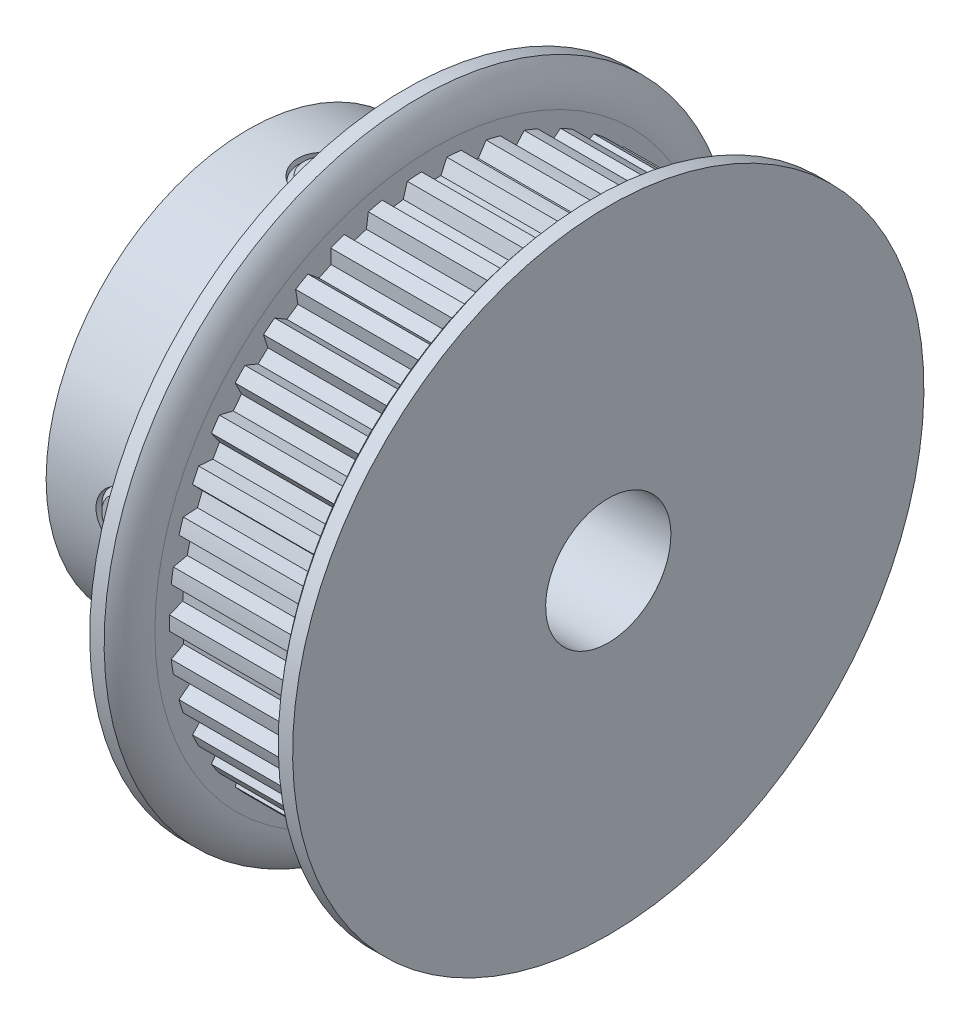
SolidWorks part; units mm, degrees
ref_plane "Front Plane" through (0, 0, 0) normal (0, 0, 1) x (1, 0, 0)
ref_plane "Top Plane" through (0, 0, 0) normal (0, 1, 0) x (1, 0, 0)
ref_plane "Right Plane" through (0, 0, 0) normal (1, 0, 0) x (0, 0, -1)
sketch "Sketch2" plane through (0, 0, 0) normal (1, 0, 0) x (0, 0, -1)
  line L3 (0, 0) -> (0, 12.7635) construction
  line L6 (0, -13.2715) -> (0, -13.589) construction
  line L7 (-0.5715, 13.2592) -> (-0.3383, 12.759)
  line L8 (0.5715, 13.2592) -> (0.3383, 12.759)
  line L9 (-0.5715, 13.2592) -> (-0.6441, 13.4148)
  line L10 (0.5715, 13.2592) -> (0.6441, 13.4148)
  line L12 (-0.3383, 12.759) -> (0.3383, 12.759)
  line L14 (0, 13.2715) -> (0, 13.589) construction
  line L15 (0, 0) -> (0, -1.143) construction
  circle A0 centre (0, 0) radius 13.589 construction
  circle A1 centre (0, 0) radius 12.7635 construction
  circle A2 centre (0, 0) radius 13.2715 construction
  arc A7 (0.6441, 13.4148) -> (-0.6441, 13.4148) centre (0, 0) ccw
  point P5 (0, 13.4303)
  dimension "D1" = 50
  dimension "PD" = 27.178
  dimension "D3" = 0.3175
  dimension "bt" = 1.143
  dimension "hs" = 1.143
  dimension "ht" = 0.508
sketch "Sketch1" plane through (0, 0, 0) normal (0, 0, 1) x (1, 0, 0)
  line L0 (-9.1313, 0) -> (9.1313, 0) construction
  line L1 (-9.1313, 3.175) -> (9.1313, 3.175)
  line L2 (-9.1313, 3.175) -> (-9.1313, 10.2362)
  line L3 (-1.1557, 16.002) -> (-0.4254, 16.002)
  line L4 (0.3048, 13.589) -> (0.3048, 14.1605)
  line L5 (0.3048, 14.732) -> (0.3048, 13.589) construction
  line L6 (0.3048, 13.589) -> (7.6708, 13.589)
  line L7 (7.6708, 13.589) -> (7.6708, 14.1605)
  line L8 (7.6708, 13.589) -> (9.1313, 13.589) construction
  line L9 (8.4011, 16.002) -> (9.1313, 16.002)
  line L10 (9.1313, 16.002) -> (9.1313, 3.175)
  line L11 (8.4011, 13.589) -> (8.4011, 16.002) construction
  line L12 (-5.1435, 10.2362) -> (-5.1435, 3.175) construction
  line L13 (-1.1557, 16.002) -> (-1.1557, 10.2362)
  line L14 (-1.1557, 10.2362) -> (-9.1313, 10.2362)
  arc A0 (7.6708, 14.1605) -> (8.4011, 16.002) centre (10.3578, 14.1605) cw
  arc A1 (0.3048, 14.1605) -> (-0.4254, 16.002) centre (-2.3822, 14.1605) ccw
  dimension "Bore Size" = 6.35
  dimension "D2" = 27.178
  dimension "Overall Width" = 18.2626
  dimension "Inside Width" = 7.366
  dimension "Outside Width" = 10.287
  dimension "Hub Dia" = 20.4724
  dimension "OD" = 32.004
  dimension "D3" = 1.143
  dimension "D4" = 0.5715
revolve "Revolve1" add sketch "Sketch1" angle 360 mid plane about L0
sketch "Sketch4" plane through (0.3048, 0, 0) normal (1, 0, 0) x (0, 0, -1)
  circle A0 centre (0, 0) radius 13.4303
  circle A2 centre (0, 0) radius 13.589
  circle A3 centre (0, 0) radius 13.589 construction
extrude "Cut-Extrude2" cut sketch "Sketch4" along normal up to surface (7.366 mm away) up to face at (7.6708, -13.589, 0)
sketch "Sketch3" plane through (0.3048, 0, 0) normal (1, 0, 0) x (0, 0, -1)
  line L2 (-0.5715, 13.2592) -> (-0.3383, 12.759) construction
  line L3 (-0.3383, 12.759) -> (0.3383, 12.759) construction
  line L4 (0.5715, 13.2592) -> (0.3383, 12.759) construction
  line L5 (-0.6441, 13.4148) -> (-0.3383, 12.759)
  line L6 (-0.3383, 12.759) -> (0.3383, 12.759)
  line L7 (0.6441, 13.4148) -> (0.3383, 12.759)
  arc A1 (0.6441, 13.4148) -> (-0.6441, 13.4148) centre (0, 0) ccw construction
  arc A2 (0.6441, 13.4148) -> (-0.6441, 13.4148) centre (0, 0) ccw
extrude "Cut-Extrude1" cut sketch "Sketch3" along normal up to surface (7.366 mm away) up to face at (7.6708, -14.1605, 0)
pattern_circular "CirPattern1" count 42 over 360 of "Cut-Extrude1"
sketch "Sketch5" plane through (0, 0, 0) normal (0, 0, 1) x (1, 0, 0)
  line L1 (7.6708, 14.1605) -> (7.6708, -14.1605) construction
  point P0 (7.6708, 0)
sketch "Sketch6" plane through (0, 0, 0) normal (0, 1, 0) x (1, 0, 0)
  line L0 (-9.1313, 0) -> (-6.604, 0) construction
  line L1 (-9.1313, 16.002) -> (-9.1313, -16.002) construction
  line L2 (-1.1557, 0) -> (-3.683, 0) construction
  line L4 (-1.1557, 16.002) -> (-1.1557, -16.002) construction
  circle A0 centre (-5.1435, 0) radius 1.4605
  dimension "D1" = 2.921
extrude "Cut-Extrude3" cut sketch "Sketch6" along normal through all
sketch "Sketch7" plane through (0, 0, 0) normal (0, 0, 1) x (1, 0, 0)
  line L0 (-6.3119, 10.2362) -> (-5.1435, 10.2362)
  line L1 (-6.5659, 9.9822) -> (-6.5659, 3.81)
  line L2 (-6.5659, 3.81) -> (-6.3119, 3.556)
  line L3 (-6.3119, 3.556) -> (-5.1435, 3.556)
  line L4 (-5.1435, 3.556) -> (-5.1435, 10.2362) construction
  line L5 (-1.1557, 10.2362) -> (-9.1313, 10.2362) construction
  line L6 (-6.5659, 9.9822) -> (-6.3119, 10.2362)
  line L8 (-5.1435, 10.2362) -> (-5.1435, 3.556)
  point P0 (-6.5659, 10.2362)
  point P4 (-6.5659, 3.556)
  dimension "D1" = 2.8448
  dimension "D2" = 0.381
revolve "Revolve2" add sketch "Sketch7" angle 360 mid plane about L4
sketch "Sketch8" plane through (0, 10.2362, 0) normal (0, 1, 0) x (1, 0, 0)
  line L1 (-5.1435, 0.8212) -> (-5.8547, 0.4106)
  line L2 (-5.8547, 0.4106) -> (-5.8547, -0.4106)
  line L3 (-5.8547, -0.4106) -> (-5.1435, -0.8212)
  line L4 (-5.1435, -0.8212) -> (-4.4323, -0.4106)
  line L5 (-4.4323, -0.4106) -> (-4.4323, 0.4106)
  line L6 (-4.4323, 0.4106) -> (-5.1435, 0.8212)
  circle A0 centre (-5.1435, 0) radius 0.7112 construction
  dimension "D1" = 1.4224
extrude "Cut-Extrude4" cut sketch "Sketch8" against normal blind 1.016
pattern_circular "CirPattern2" count 2 over 90 about axis through (-9.1313, 0, 0) along (-1, 0, 0) of "Cut-Extrude3" reverse direction yes
pattern_circular "CirPattern3" count 2 over 90 reverse direction yes of bodies 107
equation "\"D3@Sketch2\" = (\"hs@Sketch2\"-\"ht@Sketch2\")/2"
equation "\"D2@Sketch1\" = \"PD@Sketch2\""
equation "\"D3@Sketch1\" = \"hs@Sketch2\""
equation "\"D4@Sketch1\" = \"D3@Sketch1\"/2"
